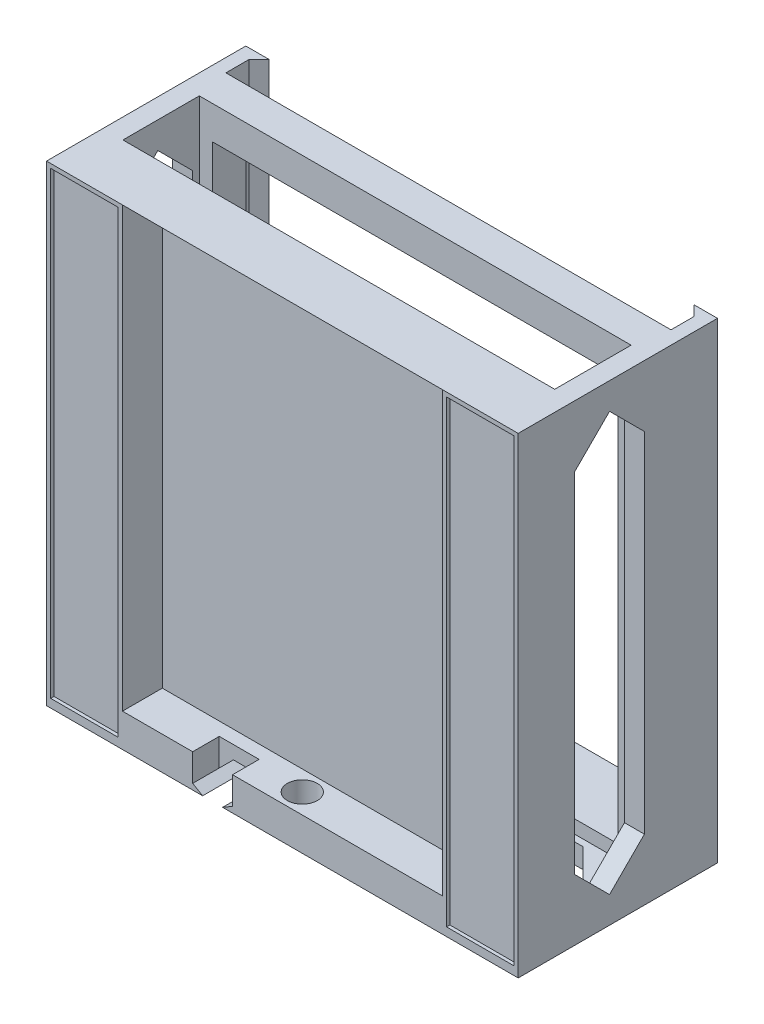
SolidWorks part; units mm, degrees
ref_plane "Front Plane" through (0, 0, 0) normal (1, 0, 0) x (0, 1, 0)
ref_plane "Top Plane" through (0, 0, 0) normal (0, 0, 1) x (0, 1, 0)
ref_plane "Right Plane" through (0, 0, 0) normal (0, 1, 0) x (-1, 0, 0)
sketch "Sketch1" plane through (0, 0, 0) normal (0, 0, 1) x (0, 1, 0)
  line L0 (-71, -71) -> (-71, 71)
  line L1 (-61, -61) -> (61, -61)
  line L2 (-61, -61) -> (-61, 61)
  line L3 (-61, 61) -> (61, 61)
  line L4 (61, -61) -> (61, 61)
  line L5 (-61, -61) -> (61, 61) construction
  line L6 (-61, 61) -> (61, -61) construction
  line L7 (-71, 71) -> (71, 71)
  line L8 (71, -71) -> (71, 71)
  line L9 (-71, -71) -> (71, -71)
  point P0 (0, 0)
  dimension "D1" = 122
  dimension "D2" = 122
  dimension "D3" = 10
extrude "Boss-Extrude1" add sketch "Sketch1" along normal blind 10
sketch "Sketch2" plane through (0, 0, 0) normal (0, 0, -1) x (1, 0, 0)
  line L1 (-71, 71) -> (71, 71)
  line L2 (71, 71) -> (71, 61)
  line L3 (71, 71) -> (71, -71) construction
  line L4 (71, 61) -> (-71, 61)
  line L5 (-71, -71) -> (-71, 71) construction
  line L6 (-71, 61) -> (-71, 71)
  line L7 (-61, 61) -> (61, 61) construction
extrude "Boss-Extrude2" add sketch "Sketch2" along normal blind 10
sketch "Sketch3" plane through (0, -61, 0) normal (0, 1, 0) x (-1, 0, 0)
  line L3 (-67, -7) -> (-64, -10)
  line L4 (71, -10) -> (-71, -10) construction
  line L5 (-64, -10) -> (-71, -10)
  line L6 (-71, -10) -> (-71, 0)
  line L7 (0, 11) -> (0, -11) construction
  line L8 (64, -10) -> (71, -10)
  line L9 (67, -7) -> (64, -10)
  line L10 (67, 0) -> (67, -7)
  line L11 (71, 0) -> (67, 0)
  line L12 (71, -10) -> (71, 0)
  line L13 (-71, 0) -> (-67, 0)
  line L14 (-61, 0) -> (-71, 0) construction
  line L15 (-67, 0) -> (-67, -7)
  dimension "D1" = 4
  dimension "D2" = 45
  dimension "D3" = 7
extrude "Boss-Extrude3" add sketch "Sketch3" along normal up to surface (132 mm away) up to face at (0, 71, 5)
sketch "Sketch4" plane through (0, 0, 10) normal (0, 0, 1) x (1, 0, 0)
  line L1 (-60, -60) -> (60, -60) construction
  line L2 (-60, -60) -> (-60, 60) construction
  line L3 (-60, 60) -> (60, 60) construction
  line L4 (60, -60) -> (60, 60) construction
  line L5 (-60, -60) -> (60, 60) construction
  line L6 (-60, 60) -> (60, -60) construction
  point P0 (0, 0)
  dimension "D1" = 120
  dimension "D2" = 120
sketch "Sketch5" plane through (0, 0, 10) normal (0, 0, 1) x (1, 0, 0)
  line L0 (71, -71) -> (71, 71) construction
  line L1 (-65, -65) -> (65, -65)
  line L2 (-65, -65) -> (-65, 65)
  line L4 (65, -65) -> (65, 65)
  line L5 (-65, -65) -> (65, 65) construction
  line L6 (-65, 65) -> (65, -65) construction
  line L7 (-71, 71) -> (-65, 71)
  line L8 (71, 71) -> (-71, 71) construction
  line L9 (-65, 71) -> (-65, 65)
  line L10 (-71, 71) -> (-71, -71)
  line L11 (-71, -71) -> (71, -71)
  line L12 (71, -71) -> (71, 65)
  line L13 (71, 65) -> (71, 71)
  line L14 (71, 71) -> (65, 71)
  line L15 (65, 71) -> (65, 65)
  point P1 (0, 0)
  dimension "D1" = 6
extrude "Boss-Extrude4" add sketch "Sketch5" along normal blind 2
sketch "Sketch6" plane through (0, 0, 12) normal (0, 0, 1) x (1, 0, 0)
  line L0 (-65, -65) -> (-65, 71) construction
  line L1 (-71, 71) -> (-65, 71)
  line L2 (-71, 71) -> (-71, 63)
  line L3 (-71, 63) -> (-65, 63)
  line L4 (-65, 71) -> (-65, 63)
  line L10 (-65, -65) -> (-65, -63)
  line L11 (-65, -63) -> (-71, -63)
  line L12 (-71, 71) -> (-71, -71) construction
  line L13 (-71, -63) -> (-71, -71)
  line L14 (-71, -71) -> (-63, -71)
  line L15 (-71, -71) -> (71, -71) construction
  line L16 (-63, -71) -> (-63, -65)
  line L17 (65, -65) -> (-65, -65) construction
  line L18 (-63, -65) -> (-65, -65)
  line L19 (0, -12.1) -> (0, 12.1) construction
  line L20 (63, -71) -> (63, -65)
  line L21 (71, -71) -> (63, -71)
  line L22 (71, -63) -> (71, -71)
  line L23 (65, -63) -> (71, -63)
  line L24 (65, -65) -> (65, -63)
  line L25 (63, -65) -> (65, -65)
  line L26 (71, 63) -> (65, 63)
  line L27 (65, 71) -> (65, 63)
  line L28 (71, 71) -> (65, 71)
  line L29 (71, 71) -> (71, 63)
  dimension "D1" = 8
  dimension "D3" = 8
  dimension "D4" = 8
extrude "Boss-Extrude5" add sketch "Sketch6" along normal blind 21
sketch "Sketch7" plane through (0, -71, 0) normal (0, -1, 0) x (1, 0, 0)
  line L0 (-63, 33) -> (63, 33)
  line L1 (63, 33) -> (71, 33)
  line L2 (71, 33) -> (71, 38)
  line L3 (71, 38) -> (-71, 38)
  line L4 (-71, 38) -> (-71, 33)
  line L5 (-71, 33) -> (-63, 33)
  dimension "D1" = 5
extrude "Boss-Extrude6" add sketch "Sketch7" against normal up to surface (142 mm away) up to face at (0, 71, 7)
sketch "Sketch8" plane through (71, 0, 0) normal (1, 0, 0) x (0, 1, 0)
  line L0 (63, 22.5) -> (52.5, 33)
  line L1 (63, 33) -> (63, 12) construction
  line L2 (63, 33) -> (-63, 33) construction
  line L3 (52.5, 33) -> (63, 33)
  line L4 (63, 33) -> (63, 22.5)
  line L5 (63, 22.5) -> (52.5, 12)
  line L6 (-63, 12) -> (63, 12) construction
  line L7 (52.5, 12) -> (63, 12)
  line L8 (63, 12) -> (63, 22.5)
  line M8 (-63, 33) -> (63, 33)
  line M9 (63, 33) -> (63, 12)
  line M10 (63, 12) -> (-63, 12)
  dimension "D1" = 45
extrude "Boss-Extrude7" add sketch "Sketch8" against normal up to surface (6 mm away) contours L5 M9 M10 | L0 M9 M8 region at (71, 59.5, 29.5) region at (71, 59.5, 15.5) up to face at (65, 1.5, 22)
sketch "Sketch9" plane through (-71, 0, 0) normal (-1, 0, 0) x (0, -1, 0)
  line L0 (-63, 33) -> (-52.5, 33)
  line L1 (-52.5, 33) -> (-63, 22.5)
  line L2 (-63, 22.5) -> (-63, 33)
  line L3 (-63, 22.5) -> (-63, 12)
  line L4 (-63, 12) -> (-52.5, 12)
  line L5 (-52.5, 12) -> (-63, 22.5)
  line M8 (-63, 33) -> (63, 33)
  line M10 (63, 12) -> (-63, 12)
  line M11 (-63, 12) -> (-63, 33)
extrude "Boss-Extrude8" add sketch "Sketch9" against normal up to surface (6 mm away) contours L5 M10 M11 | L1 M8 M11 region at (-71, 59.5, 15.5) region at (-71, 59.5, 29.5) up to face at (-65, 1.5, 22)
mirror "Mirror4" about plane through (0, 0, 0) normal (0, 1, 0) of "Boss-Extrude8", "Boss-Extrude7"
sketch "Sketch10" plane through (0, 0, 38) normal (0, 0, 1) x (1, 0, 0)
  line L0 (-48.14, 59) -> (-48.14, -48.14)
  line L2 (48.14, -48.14) -> (48.14, 59)
  line L4 (71, 71) -> (-71, 71)
  line L5 (-71, 71) -> (-71, -71)
  line L6 (-71, -71) -> (71, -71)
  line L7 (71, -71) -> (71, 71)
  line L9 (-71, 71) -> (-71, -71)
  line L10 (-71, -71) -> (71, -71)
  line L11 (71, -71) -> (71, 71)
  line L13 (-48.14, 48.14) -> (-48.14, -48.14) construction
  line L14 (48.14, -48.14) -> (48.14, 48.14) construction
  line L15 (-71, 71) -> (71, 71)
  line L16 (48.14, 48.14) -> (-48.14, 48.14) construction
  line L17 (-48.14, 59) -> (48.14, 59)
  line L19 (-48.14, -48.14) -> (-48.14, -61)
  line L20 (-48.14, -48.14) -> (48.14, -48.14) construction
  line L21 (71, 71) -> (-71, 71) construction
  line L22 (-48.14, -61) -> (48.14, -61)
  line L23 (48.14, -61) -> (48.14, -48.14)
  dimension "D3" = 12
  dimension "D4" = 10
  dimension "D1" = 0
  dimension "D2" = 22.86
extrude "Boss-Extrude9" add sketch "Sketch10" along normal blind 12
sketch "Sketch11" plane through (0, -71, 0) normal (0, -1, 0) x (1, 0, 0)
  line L0 (-63, 22.5) -> (-52.5, 12)
  line L1 (-63, 33) -> (-63, 12) construction
  line L2 (-63, 12) -> (63, 12) construction
  line L3 (-52.5, 12) -> (-63, 12)
  line L4 (-63, 22.5) -> (-63, 12)
  line L5 (-63, 22.5) -> (-63, 33)
  line L6 (-63, 33) -> (-52.5, 33)
  line L7 (-63, 33) -> (63, 33) construction
  line L8 (-52.5, 33) -> (-63, 22.5)
  dimension "D1" = 45
extrude "Boss-Extrude14" add sketch "Sketch11" against normal up to surface (6 mm away) contours L0 | L6 region at (-59.5, -71, 15.5) region at (-59.5, -71, 29.5) up to face at (0, -65, 22)
mirror "Mirror5" about plane through (0, 0, 0) normal (1, 0, 0) of "Boss-Extrude14"
sketch "Sketch13" plane through (0, -61, 0) normal (0, 1, 0) x (-1, 0, 0)
  line L0 (0, 50) -> (0, 38) construction
  line L1 (48.14, 50) -> (-48.14, 50) construction
  line L2 (48.14, 38) -> (-48.14, 38) construction
  circle A0 centre (0, 44) radius 4.5
  dimension "D1" = 9
extrude "Cut-Extrude2" cut sketch "Sketch13" against normal through all
sketch "Sketch14" plane through (0, 0, 50) normal (0, 0, 1) x (1, 0, 0)
  line L0 (71, 71) -> (-71, 71) construction
  line L1 (-49.41, 69.73) -> (-69.73, 69.73)
  line L2 (-49.41, 69.73) -> (-49.41, -68.46)
  line L3 (-49.41, -68.46) -> (-69.73, -68.46)
  line L4 (-69.73, 69.73) -> (-69.73, -68.46)
  line L5 (-71, 71) -> (-71, -71) construction
  line L7 (-71, -71) -> (71, -71) construction
  line L8 (0, -33) -> (0, 33) construction
  line L9 (49.41, -68.46) -> (69.73, -68.46)
  line L10 (69.73, 69.73) -> (69.73, -68.46)
  line L11 (49.41, 69.73) -> (69.73, 69.73)
  line L12 (49.41, 69.73) -> (49.41, -68.46)
  dimension "D1" = 1.27
  dimension "D2" = 1.27
  dimension "D3" = 20.32
  dimension "D4" = 2.54
extrude "Cut-Extrude3" cut sketch "Sketch14" against normal blind 1
chamfer "Chamfer4" distance 12 angle 45 1 edges at (0, 59, 50)
sketch "Sketch15" plane through (0, 0, 50) normal (0, 0, 1) x (1, 0, 0)
  line L0 (-24, -71) -> (-18, -71)
  line L1 (-71, -71) -> (71, -71) construction
  line L2 (-18, -71) -> (-15, -69.2549)
  line L3 (-15, -69.2549) -> (-19.2549, -65)
  line L4 (-19.2549, -65) -> (-22.7451, -65)
  line L5 (-22.7451, -65) -> (-27, -69.2549)
  line L6 (-27, -69.2549) -> (-24, -71)
  line L7 (0, -71) -> (0, -61) construction
  line L8 (-48.14, -61) -> (48.14, -61) construction
  point P4 (-21, -71)
  point P9 (-21, -65)
  dimension "D1" = 45
  dimension "D2" = 45
  dimension "D3" = 6
  dimension "D4" = 6
  dimension "D5" = 15
  dimension "D6" = 12
extrude "Cut-Extrude4" cut sketch "Sketch15" against normal through all
sketch "Sketch16" plane through (0, -61, 0) normal (0, 1, 0) x (-1, 0, 0)
  line L0 (48.14, 50) -> (-48.14, 50) construction
  line L1 (15, 50) -> (27, 50)
  line L2 (15, 50) -> (15, 42)
  line L3 (15, 42) -> (27, 42)
  line L4 (27, 50) -> (27, 42)
  point P6 (0, 0)
  point P8 (0, 0)
  dimension "D1" = 8
extrude "Cut-Extrude5" cut sketch "Sketch16" against normal up to vertex (8.2549 mm away) up to point (-15, -69.2549, 50)
